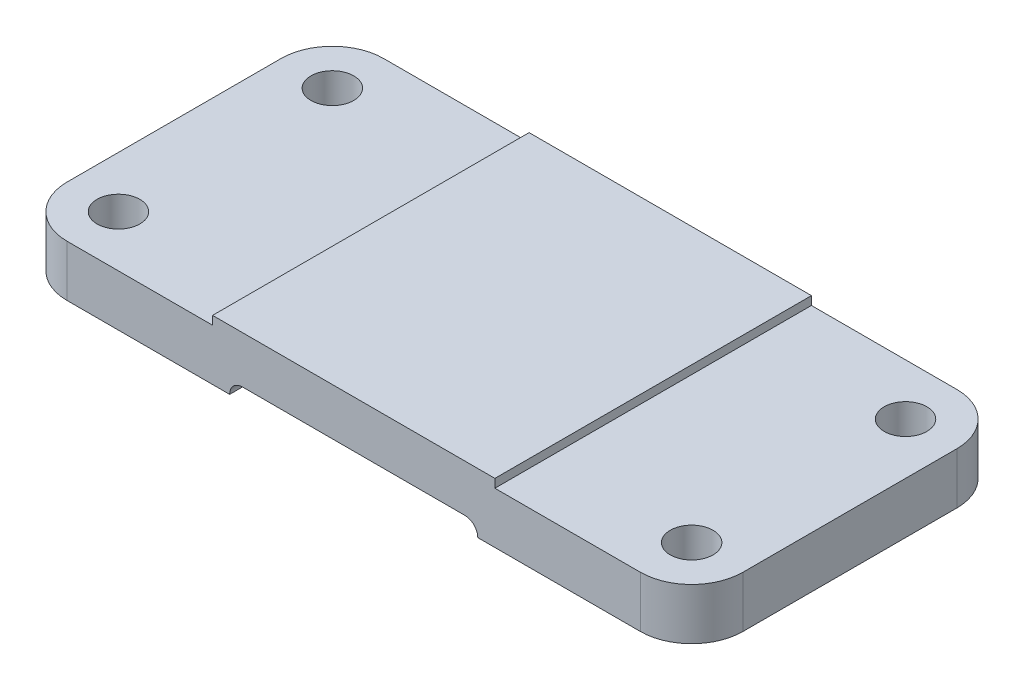
SolidWorks part; units mm, degrees
ref_plane "Front Plane" through (0, 0, 0) normal (0, 0, 1) x (1, 0, 0)
ref_plane "Top Plane" through (0, 0, 0) normal (0, 1, 0) x (1, 0, 0)
ref_plane "Right Plane" through (0, 0, 0) normal (1, 0, 0) x (0, 0, -1)
sketch "Sketch1" plane through (0, 0, 0) normal (0, 1, 0) x (1, 0, 0)
  line L1 (-76.8652, 28.0264) -> (57.1348, 28.0264)
  line L2 (-88.8652, 16.0264) -> (-88.8652, -33.9736)
  line L3 (-76.8652, -45.9736) -> (57.1348, -45.9736)
  line L4 (69.1348, 16.0264) -> (69.1348, -33.9736)
  arc A0 (-88.8652, -33.9736) -> (-76.8652, -45.9736) centre (-76.8652, -33.9736) ccw
  arc A1 (-88.8652, 16.0264) -> (-76.8652, 28.0264) centre (-76.8652, 16.0264) cw
  arc A2 (69.1348, 16.0264) -> (57.1348, 28.0264) centre (57.1348, 16.0264) ccw
  arc A3 (57.1348, -45.9736) -> (69.1348, -33.9736) centre (57.1348, -33.9736) ccw
extrude "Boss-Extrude1" add sketch "Sketch1" along normal blind 12
sketch "Sketch2" plane through (0, 12, 0) normal (0, 1, 0) x (-1, 0, 0)
  line L0 (9.8652, -28.0264) -> (42.8652, -28.0264)
  line L1 (-57.1348, -28.0264) -> (76.8652, -28.0264) construction
  line L2 (9.8652, -28.0264) -> (-23.1348, -28.0264)
  line L3 (42.8652, -28.0264) -> (42.8652, 45.9736)
  line L4 (76.8652, 45.9736) -> (-57.1348, 45.9736) construction
  line L5 (42.8652, 45.9736) -> (-23.1348, 45.9736)
  line L6 (-23.1348, 45.9736) -> (-23.1348, -28.0264)
extrude "Boss-Extrude2" add sketch "Sketch2" along normal blind 2
sketch "Sketch3" plane through (0, 0, 0) normal (0, -1, 0) x (1, 0, 0)
  line L0 (-9.8652, 45.9736) -> (19.1348, 45.9736)
  line L1 (-76.8652, 45.9736) -> (57.1348, 45.9736) construction
  line L2 (-9.8652, 45.9736) -> (-38.8652, 45.9736)
  line L3 (-38.8652, 45.9736) -> (-38.8652, -28.0264)
  line L4 (57.1348, -28.0264) -> (-76.8652, -28.0264) construction
  line L5 (19.1348, 45.9736) -> (19.1348, -28.0264)
  line L6 (19.1348, -28.0264) -> (-38.8652, -28.0264)
extrude "Cut-Extrude1" cut sketch "Sketch3" against normal blind 3
fillet "Fillet1" radius 3 1 edges at (-38.8652, 3, 8.9736)
fillet "Fillet2" radius 3 1 edges at (19.1348, 3, 8.9736)
hole_wizard "Hole2" positions "Sketch20" profile "Sketch21" legacy end condition through all
sketch "Sketch20" plane through (0, 12, 0) normal (0, 1, 0) x (-1, 0, 0)
  point P0 (76.8652, -16.0264)
sketch "Sketch21" plane through (-76.8652, 12, -16.0264) normal (1, 0, 0) x (0, 0, 1)
  line L0 (0, 0) -> (0, 12)
  line L1 (0, 12) -> (5, 12)
  line L2 (5, 12) -> (5, 0)
  line L3 (5, 0) -> (0, 0)
  line L4 (0, 110) -> (0, -10) construction
  dimension "Diameter" = 10
  dimension "Depth" = 12
hole_wizard "Hole3" positions "Sketch23" profile "Sketch22" legacy
sketch "Sketch23" plane through (0, 12, 0) normal (0, 1, 0) x (-1, 0, 0)
  point P0 (76.8652, 33.9736)
sketch "Sketch22" plane through (-76.8652, 12, 33.9736) normal (1, 0, 0) x (0, 0, 1)
  line L0 (0, 0) -> (0, 12)
  line L1 (0, 12) -> (5, 12)
  line L2 (5, 12) -> (5, 0)
  line L3 (5, 0) -> (0, 0)
  line L4 (0, 110) -> (0, -10) construction
  dimension "Diameter" = 10
  dimension "Depth" = 12
hole_wizard "Hole4" positions "Sketch25" profile "Sketch24" legacy
sketch "Sketch25" plane through (0, 12, 0) normal (0, 1, 0) x (-1, 0, 0)
  point P0 (-57.1348, 33.9736)
sketch "Sketch24" plane through (57.1348, 12, 33.9736) normal (1, 0, 0) x (0, 0, 1)
  line L0 (0, 0) -> (0, 12)
  line L1 (0, 12) -> (5, 12)
  line L2 (5, 12) -> (5, 0)
  line L3 (5, 0) -> (0, 0)
  line L4 (0, 110) -> (0, -10) construction
  dimension "Diameter" = 10
  dimension "Depth" = 12
hole_wizard "Hole5" positions "Sketch27" profile "Sketch26" legacy
sketch "Sketch27" plane through (0, 12, 0) normal (0, 1, 0) x (-1, 0, 0)
  point P0 (-57.1348, -16.0264)
sketch "Sketch26" plane through (57.1348, 12, -16.0264) normal (1, 0, 0) x (0, 0, 1)
  line L0 (0, 0) -> (0, 12)
  line L1 (0, 12) -> (5, 12)
  line L2 (5, 12) -> (5, 0)
  line L3 (5, 0) -> (0, 0)
  line L4 (0, 110) -> (0, -10) construction
  dimension "Diameter" = 10
  dimension "Depth" = 12
